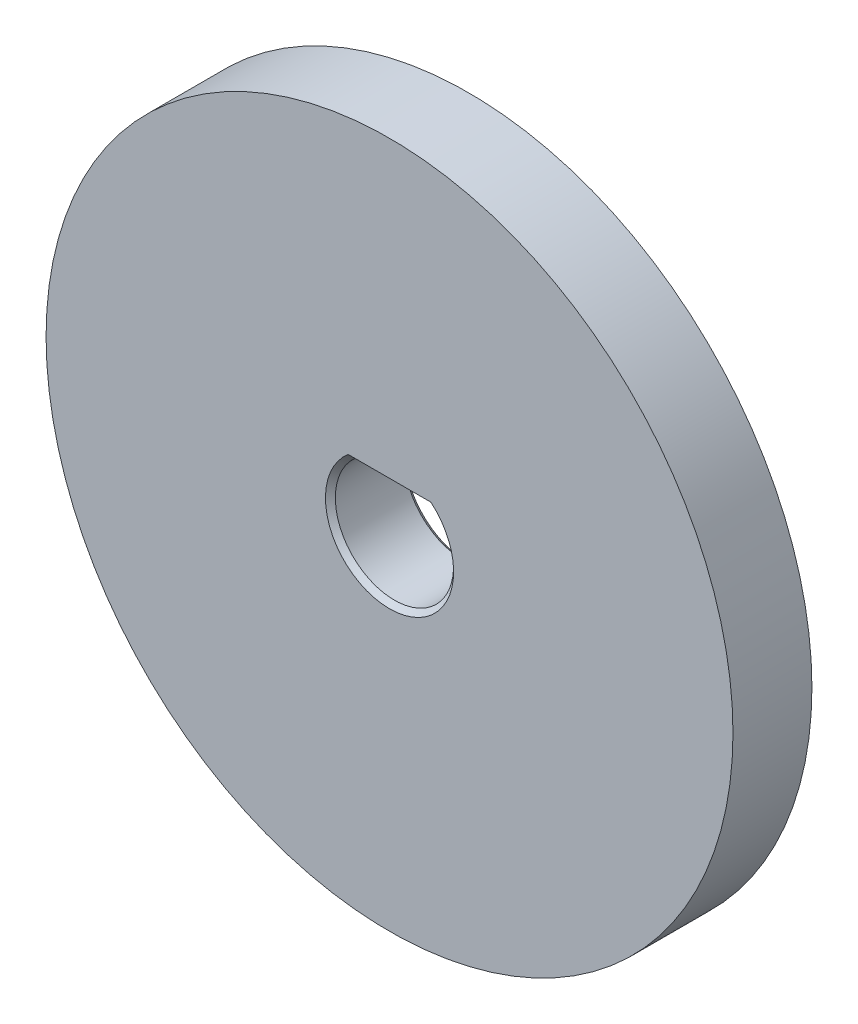
SolidWorks part; units mm, degrees
material "6061-T6 (SS)"
ref_plane "Front Plane" through (0, 0, 0) normal (0, 0, 1) x (1, 0, 0)
ref_plane "Top Plane" through (0, 0, 0) normal (0, 1, 0) x (1, 0, 0)
ref_plane "Right Plane" through (0, 0, 0) normal (1, 0, 0) x (0, 0, -1)
sketch "Sketch1" plane through (0, 0, 0) normal (0, 0, 1) x (1, 0, 0)
  circle A0 centre (0, 0) radius 55.245
  circle A1 centre (0, 0) radius 9.5123
  dimension "D1" = 110.49
  dimension "D2" = 19.0246
extrude "Extrude1" add sketch "Sketch1" along normal mid plane 12.7
sketch "Sketch2" plane through (0, 0, 0) normal (1, 0, 0) x (0, 0, -1)
  line L0 (-4.7625, 47.625) -> (4.7625, 47.625)
  line L2 (4.7625, 47.625) -> (2.4513, 41.275)
  line L3 (2.4513, 41.275) -> (-2.4513, 41.275)
  line L4 (-2.4513, 41.275) -> (-4.7625, 47.625)
  line L5 (-6.35, 0) -> (6.35, 0) construction
  line L6 (-6.35, 55.245) -> (-6.35, -55.245) construction
  line L7 (6.35, -55.245) -> (6.35, 55.245) construction
  point P2 (0, 47.625)
  point P5 (0, 41.275)
  dimension "D1" = 47.625
  dimension "D2" = 6.35
  dimension "D3" = 9.525
  dimension "D4" = 40
sketch "Sketch3" plane through (0, 0, -6.35) normal (0, 0, -1) x (-1, 0, 0)
  line L0 (-6.3595, 7.0739) -> (6.3595, 7.0739)
  line L1 (0, 7.0739) -> (0, -9.5123) construction
  circle A0 centre (0, 0) radius 9.5123 construction
  circle A2 centre (0, 0) radius 9.5123
  arc A3 (6.3595, 7.0739) -> (-6.3595, 7.0739) centre (0, 0) ccw
  dimension "D1" = 16.5862
  dimension "D2" = 0
extrude "Boss-Extrude1" add sketch "Sketch3" against normal up to surface (12.7 mm away) up to face at (55.245, 0, 6.35)
chamfer "Chamfer3" distance 0.795 angle 45 4 edges at (0, -9.5123, 6.35) (0, 7.0739, 6.35) (0, 7.0739, -6.35) (0, -9.5123, -6.35)
